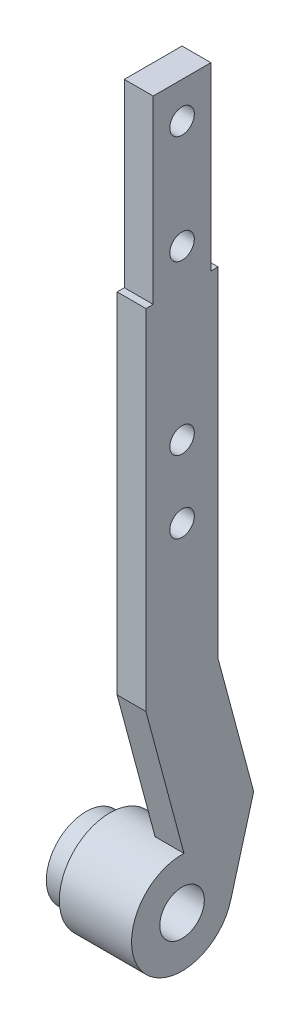
SolidWorks part; units mm, degrees
ref_plane "Front" through (0, 0, 0) normal (0, 0, 1) x (1, 0, 0)
ref_plane "Top" through (0, 0, 0) normal (0, 1, 0) x (1, 0, 0)
ref_plane "Right" through (0, 0, 0) normal (1, 0, 0) x (0, 0, -1)
sketch "Sketch1" plane through (-20.145, 0, 0) normal (-1, 0, 0) x (0, 0, 1)
  line L0 (-5, 27.967) -> (-9.926, 9.5831)
  line L1 (5, 26.6505) -> (5, 100)
  line L2 (5, 100) -> (-5, 100)
  line L3 (-5, 100) -> (-5, 27.967)
  line L4 (-0.2667, 6.9949) -> (5, 26.6505)
  line L5 (-9.926, 9.5831) -> (-6.7448, -1.8729)
  line L6 (5, 75) -> (-5, 75) construction
  line L7 (0, 0) -> (0, 100) construction
  line L8 (-5, 87.5) -> (5, 87.5) construction
  line L9 (0, 95) -> (0, 80) construction
  line L10 (-5, 75) -> (-4, 75)
  line L11 (-4, 75) -> (-4, 100)
  line L12 (5, 75) -> (4, 75)
  line L13 (4, 75) -> (4, 100)
  circle A0 centre (0, 80) radius 1.7
  circle A1 centre (0, 95) radius 1.7
  circle A6 centre (0, 0) radius 3.0845
  arc A7 (-3.0391, 0.5274) -> (2.6861, -1.5163) centre (0, 0) ccw
  arc A8 (-3.0391, 0.5274) -> (2.6861, -1.5163) centre (0, 0) ccw construction
  circle A9 centre (0, 0) radius 7
  point P20 (0, 87.5)
  dimension "D2" = 14
  dimension "D7" = 3.4
  dimension "D8" = 3.4
  dimension "D3" = 10
  dimension "D4" = 10
  dimension "D5" = 10
  dimension "D6" = 100
  dimension "D9" = 15
  dimension "D10" = 25
  dimension "D11" = 1
  dimension "D1" = 0.1
extrude "Boss-Extrude1" add sketch "Sketch1" along normal blind 10 contours A9 A6 region at (-20.145, 4.0124, -5.4925)
extrude "Boss-Extrude2" add sketch "Sketch1<3>" against normal blind 3 from surface contours A9 starting at face at (-30.145, 0, 3.0845)
sketch "Sketch1<3>" plane through (-20.145, 0, 0) normal (-1, 0, 0) x (0, 0, 1) same geometry as "Sketch1"
extrude "Boss-Extrude3" add sketch "Sketch1<5>" along normal blind 4 contours A9 L4 L1 L2 L3 L0 L5 region at (-20.145, 49.6264, -0.767)
sketch "Sketch1<5>" plane through (-20.145, 0, 0) normal (-1, 0, 0) x (0, 0, 1) same geometry as "Sketch1"
sketch "Sketch2" plane through (-30.145, 0, 0) normal (-1, 0, 0) x (0, 0, 1)
  circle A1 centre (0, 0) radius 5.5
  circle A2 centre (0, 0) radius 3.5
  circle A3 centre (0, 0) radius 3.5
  dimension "D1" = 2
  dimension "D2" = 2
extrude "Boss-Extrude4" add sketch "Sketch2" along normal up to surface (3.305 mm away)
sketch "Sketch3" plane through (-20.145, 0, 0) normal (1, 0, 0) x (0, 0, -1)
  circle A0 centre (0, 46.748) radius 1.7
  circle A1 centre (0, 56.748) radius 1.7
  circle A3 centre (0, 46.748) radius 1.6 construction
  circle A4 centre (0, 56.748) radius 1.7 construction
  point P10 (0, 0)
  dimension "D3" = 3.4
  dimension "D4" = 3.4
extrude "Cut-Extrude1" cut sketch "Sketch3" against normal up to surface (4 mm away) contours A1 | A0 up to face at (-24.145, 51.8992, -1.7349)
equation "\"D4@Sketch3\"=\"D3@Sketch3\""
